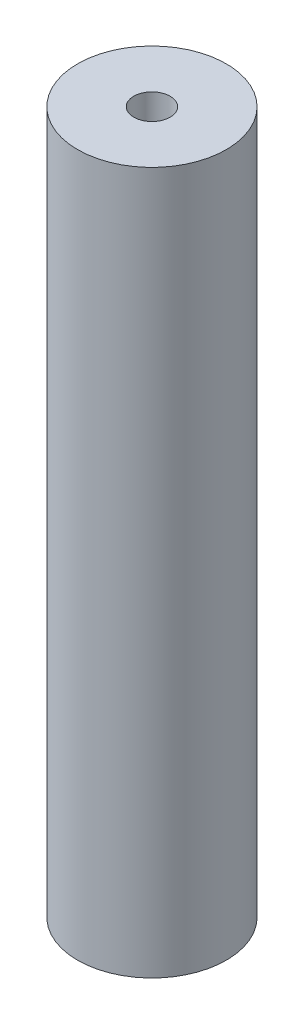
SolidWorks part; units mm, degrees
ref_plane "Front Plane" through (0, 0, 0) normal (0, 0, 1) x (1, 0, 0)
ref_plane "Top Plane" through (0, 0, 0) normal (0, 1, 0) x (1, 0, 0)
ref_plane "Right Plane" through (0, 0, 0) normal (1, 0, 0) x (0, 0, -1)
sketch "Sketch1" plane through (0, 0, 0) normal (0, 1, 0) x (1, 0, 0)
  circle A0 centre (0, 0) radius 11.65
  dimension "D1" = 23.3
extrude "Boss-Extrude1" add sketch "Sketch1" along normal blind 110
sketch "Sketch2" plane through (0, 110, 0) normal (0, 1, 0) x (1, 0, 0)
  circle A0 centre (0, 0) radius 2.85
  dimension "D1" = 5.7
extrude "Cut-Extrude1" cut sketch "Sketch2" against normal blind 110
